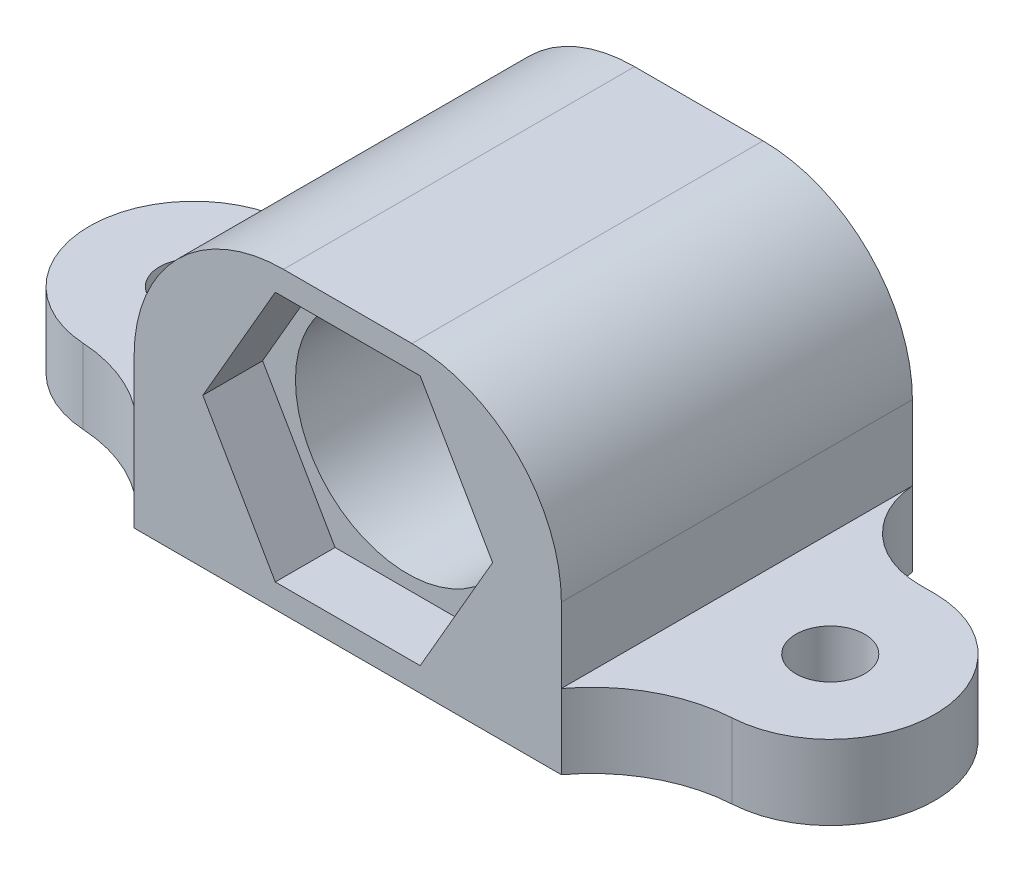
SolidWorks part; units mm, degrees
ref_plane "Front Plane" through (0, 0, 0) normal (0, 0, 1) x (1, 0, 0)
ref_plane "Top Plane" through (0, 0, 0) normal (0, 1, 0) x (1, 0, 0)
ref_plane "Right Plane" through (0, 0, 0) normal (1, 0, 0) x (0, 0, -1)
sketch "Sketch1" plane through (0, 0, 0) normal (0, 1, 0) x (1, 0, 0)
  line L0 (0, 0) -> (42.6, 0) construction
  line L1 (0, 7) -> (42.6, 7)
  line L2 (0, -7) -> (42.6, -7)
  arc A0 (0, 7) -> (0, -7) centre (0, 0) ccw
  arc A1 (42.6, -7) -> (42.6, 7) centre (42.6, 0) ccw
  circle A2 centre (0, 0) radius 2.3
  circle A3 centre (42.6, 0) radius 2.3
  point P3 (21.3, 0)
  point P12 (2.3, 0)
  point P13 (40.3, 0)
  dimension "D2" = 4.6
  dimension "D3" = 4.6
  dimension "D4" = 7
  dimension "D1" = 38
extrude "Boss-Extrude1" add sketch "Sketch1" along normal blind 9.5
sketch "Sketch2" plane through (0, 9.5, 0) normal (0, 1, 0) x (1, 0, 0)
  line L0 (0, 7) -> (42.6, 7) construction
  line L1 (0, -7) -> (42.6, -7) construction
  line L6 (7, 0) -> (35.6, 0) construction
  line L7 (7, 12.5) -> (35.6, 12.5)
  line L8 (7, -7) -> (35.6, -7)
  line L9 (7, -7) -> (7, 12.5)
  line L10 (35.6, 12.5) -> (35.6, -7)
  arc A0 (0, -7) -> (0, 7) centre (0, 0) ccw construction
  arc A1 (42.6, 7) -> (42.6, -7) centre (42.6, 0) ccw construction
  arc A2 (0, 7) -> (0, -7) centre (0, 0) ccw construction
  point P13 (7, 0)
  point P16 (35.6, 0)
  point P19 (21.3, 7)
  point P20 (21.4226, 12.5)
  dimension "D1" = 19.5
  dimension "D2" = 28.6
extrude "Boss-Extrude2" add sketch "Sketch2" along normal blind 15 and the other way through all
sketch "Sketch3" plane through (0, 0, -12.5) normal (0, 0, -1) x (-1, 0, 0)
  line L0 (-35.6, 0) -> (-7, 0) construction
  line L1 (-35.6, 24.5) -> (-35.6, 9.5)
  line L6 (-49.6, 9.5) -> (-35.6, 9.5)
  line L8 (-35.6, 24.5) -> (-7, 24.5) construction
  line L10 (-35.6, 0) -> (-35.6, 24.5) construction
  line L11 (-35.6, 24.5) -> (-7, 24.5) construction
  circle A0 centre (-21.3, 14.5) radius 7.5
  point P0 (-21.3, 24.5)
  point P10 (-35.6, 17)
  point P11 (-21.3, 14.5)
  dimension "D1" = 15
  dimension "D2" = 14.5
extrude "Cut-Extrude1" cut sketch "Sketch3" against normal through all contours A0 region at (21.3, 14.5, -12.5)
fillet "Fillet1" radius 10 2 edges at (7, 24.5, -2.75) (35.6, 24.5, -2.75)
fillet "Fillet2" radius 6 2 edges at (7, 4.75, -7) (35.6, 4.75, -7)
sketch "Sketch5" plane through (0, 0, -12.5) normal (0, 0, -1) x (-1, 0, 0)
  line L0 (7, 0) -> (7, 9.5) construction
  line L1 (-49.6, 0) -> (7, 0)
  line L2 (-49.6, 0) -> (-49.6, 4.5)
  line L3 (-49.6, 4.5) -> (7, 4.5)
  line L4 (7, 0) -> (7, 4.5)
  dimension "D1" = 4.5
extrude "Cut-Extrude2" cut sketch "Sketch5" against normal up to next
sketch "Sketch9" plane through (0, 4.5, 0) normal (0, -1, 0) x (1, 0, 0)
  line L0 (0, 0) -> (42.6, 0)
sketch "Sketch10" plane through (0, 0, 7) normal (0, 0, -1) x (-1, 0, 0)
  line L0 (-25.6, 24.5) -> (-17, 24.5) construction
  line L1 (-16.4503, 22.9) -> (-26.1497, 22.9)
  line L2 (-26.1497, 22.9) -> (-30.9995, 14.5)
  line L3 (-30.9995, 14.5) -> (-26.1497, 6.1)
  line L4 (-26.1497, 6.1) -> (-16.4503, 6.1)
  line L5 (-16.4503, 6.1) -> (-11.6005, 14.5)
  line L6 (-11.6005, 14.5) -> (-16.4503, 22.9)
  line L7 (-35.6, 4.5) -> (-35.6, 14.5)
  line L8 (-35.6, 4.5) -> (-7, 4.5)
  line L9 (-7, 4.5) -> (-7, 14.5)
  line L10 (-25.6, 24.5) -> (-17, 24.5)
  circle A0 centre (-21.3, 14.5) radius 8.4 construction
  arc A1 (-25.6, 24.5) -> (-35.6, 14.5) centre (-25.6, 14.5) ccw construction
  arc A2 (-7, 14.5) -> (-17, 24.5) centre (-17, 14.5) ccw
  arc A3 (-35.6, 14.5) -> (-25.6, 24.5) centre (-25.6, 14.5) cw
  dimension "D1" = 8.4
extrude "Boss-Extrude3" add sketch "Sketch10" against normal blind 4
sketch "Sketch11" plane through (0, 4.5, 0) normal (0, -1, 0) x (1, 0, 0)
  line L0 (0, 0) -> (7, 11)
  line L1 (7, 11) -> (35.6, 11)
  line L2 (35.6, 11) -> (42.6, 0)
  line L3 (42.6, 0) -> (0, 0)
fillet "Fillet3" radius 10 2 edges at (35.6, 7, 7) (7, 7, 7)
